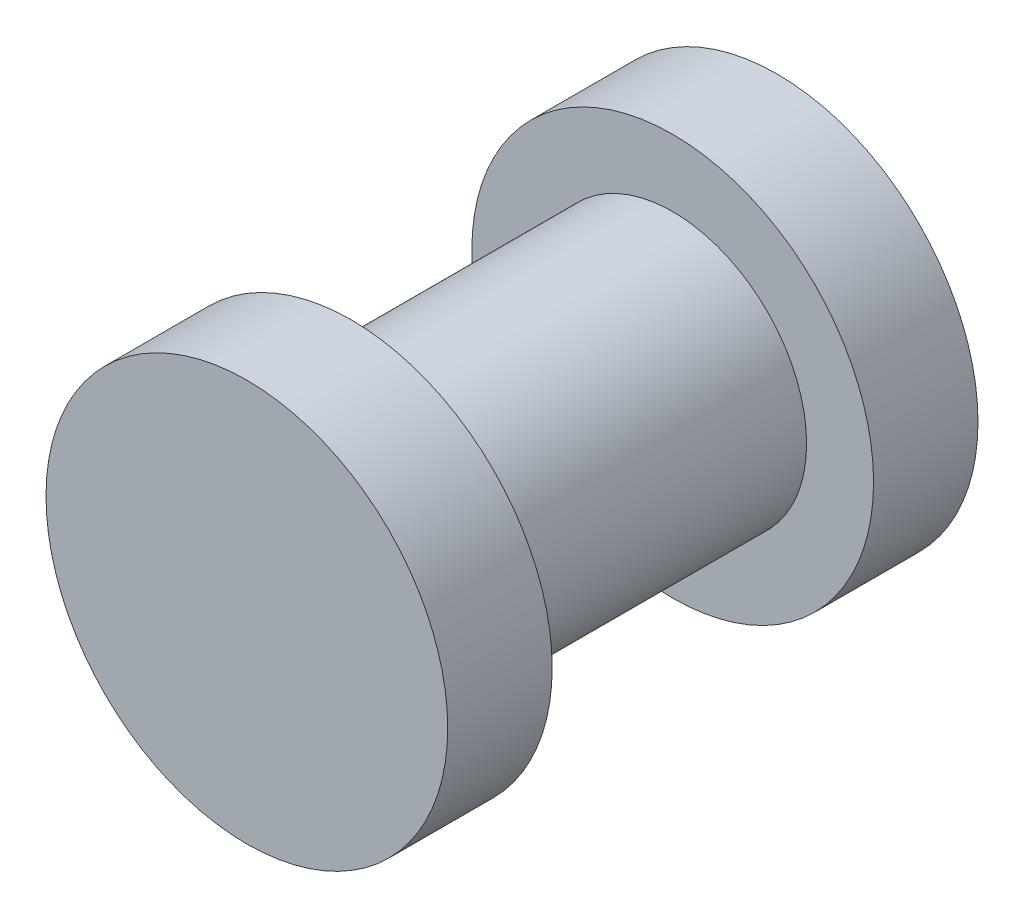
SolidWorks part; units mm, degrees
ref_plane "Front Plane" through (0, 0, 0) normal (0, 0, 1) x (1, 0, 0)
ref_plane "Top Plane" through (0, 0, 0) normal (0, 1, 0) x (1, 0, 0)
ref_plane "Right Plane" through (0, 0, 0) normal (1, 0, 0) x (0, 0, -1)
sketch "Sketch1" plane through (0, 0, 0) normal (0, 0, 1) x (1, 0, 0)
  circle A0 centre (0, 0) radius 5
  circle A1 centre (0, 0) radius 7.5
  dimension "D1" = 10
  dimension "D2" = 15
extrude "Boss-Extrude1" add sketch "Sketch1" along normal blind 19.8 contours A0 | A1 A0 region at (0, 0, 0) region at (-7.2879, 0, 0)
extrude "Cut-Extrude1" cut sketch "Sketch1<6>" along normal offset from surface (12 mm away) 3.9 from offset 3.9 contours A1 A0 region at (-7.2879, 0, 0) up to face at (7.5, 0, 19.8)
sketch "Sketch1<6>" plane through (0, 0, 0) normal (0, 0, 1) x (1, 0, 0) same geometry as "Sketch1"
